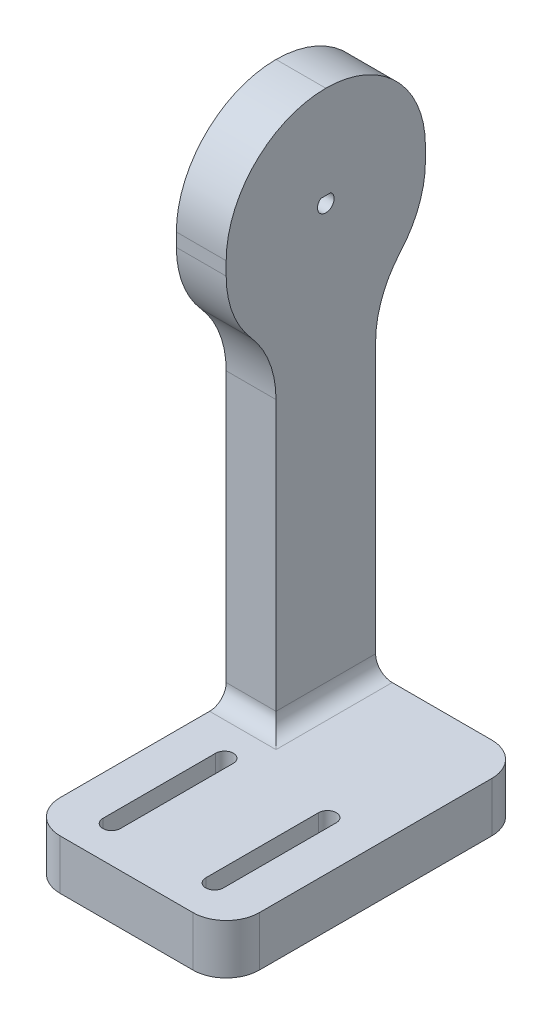
SolidWorks part; units mm, degrees
ref_plane "Front Plane" through (0, 0, 0) normal (0, 0, 1) x (1, 0, 0)
ref_plane "Top Plane" through (0, 0, 0) normal (0, 1, 0) x (1, 0, 0)
ref_plane "Right Plane" through (0, 0, 0) normal (1, 0, 0) x (0, 0, -1)
sketch "Sketch1" plane through (0, 0, 0) normal (1, 0, 0) x (0, 0, -1)
  line L1 (30, -30) -> (-30, -30)
  line L2 (30, -30) -> (30, 30)
  line L3 (30, 30) -> (-30, 30)
  line L4 (-30, -30) -> (-30, 30)
  line L5 (30, -30) -> (-30, 30) construction
  line L6 (30, 30) -> (-30, -30) construction
  point P0 (0, 0)
  dimension "D1" = 60
  dimension "D2" = 60
extrude "Boss-Extrude1" add sketch "Sketch1" along normal blind 15
sketch "Sketch2" plane through (15, 0, 0) normal (1, 0, 0) x (0, 0, -1)
  line L0 (0, 0) -> (0, 30) construction
  line L1 (30, 30) -> (-30, 30) construction
  line L2 (1.5, 2) -> (-1.5, 2)
  circle A0 centre (0, 0) radius 2.5
  dimension "D1" = 5
  dimension "D2" = 3
extrude "Cut-Extrude1" cut sketch "Sketch2" against normal up to surface (15 mm away) contours A0 region at (15, -0.1209, 0) up to face at (0, 0, 0)
sketch "Sketch8" plane through (0, -30, 0) normal (0, -1, 0) x (1, 0, 0)
  line L0 (0, 30) -> (0, 15) construction
  line L1 (0, 30) -> (0, -30) construction
  line L2 (15, 30) -> (15, -30) construction
  line L3 (0, 15) -> (15, 15)
  line L4 (0, 15) -> (0, -15)
  line L5 (0, -15) -> (15, -15)
  line L6 (15, 15) -> (15, -15)
  line L7 (0, -15) -> (0, -30) construction
  dimension "D1" = 30
extrude "Boss-Extrude2" add sketch "Sketch8" along normal blind 100
sketch "Sketch9" plane through (0, -130, 0) normal (0, -1, 0) x (1, 0, 0)
  line L0 (0, 0) -> (0, 75)
  line L1 (0, 15) -> (0, -15) construction
  line L2 (0, 75) -> (60, 75)
  line L3 (60, 75) -> (60, -15)
  line L4 (60, -15) -> (0, -15)
  line L5 (0, -15) -> (0, 0)
  dimension "D1" = 75
  dimension "D2" = 60
  dimension "D3" = 15
extrude "Boss-Extrude3" add sketch "Sketch9" along normal blind 15
sketch "Sketch10" plane through (0, -130, 0) normal (0, 1, 0) x (1, 0, 0)
  line L0 (60, -75) -> (42.85, -75) construction
  line L1 (60, -75) -> (0, -75) construction
  line L2 (42.85, -75) -> (17.15, -75) construction
  line L3 (17.15, -75) -> (0, -75) construction
  line L4 (42.85, -75) -> (42.85, -64) construction
  line L5 (42.85, -64) -> (45.5, -64) construction
  line L6 (48.15, -64) -> (48.15, -30)
  line L7 (42.85, -64) -> (42.85, -30)
  line L8 (42.85, -47) -> (48.15, -47) construction
  line L9 (30, -75) -> (30, -40.6705) construction
  line L10 (17.15, -64) -> (17.15, -30)
  line L11 (11.85, -64) -> (11.85, -30)
  arc A0 (42.85, -64) -> (48.15, -64) centre (45.5, -64) ccw
  arc A1 (42.85, -30) -> (48.15, -30) centre (45.5, -30) cw
  arc A2 (17.15, -30) -> (11.85, -30) centre (14.5, -30) ccw
  arc A3 (17.15, -64) -> (11.85, -64) centre (14.5, -64) cw
  dimension "D1" = 25.7
  dimension "D2" = 11
  dimension "D3" = 2.65
  dimension "D4" = 34
extrude "Cut-Extrude4" cut sketch "Sketch10" against normal up to surface (15 mm away) up to face at (30, -145, 30)
fillet "Fillet1" radius 30 4 edges at (7.5, 30, 30) (7.5, -30, 30) (7.5, -30, -30) (7.5, 30, -30)
fillet "Fillet3" radius 5 2 edges at (7.5, -130, 15) (15, -130, 0)
fillet "Fillet4" radius 10 3 edges at (60, -137.5, 75) (0, -137.5, 75) (60, -137.5, -15)
fillet "Fillet5" radius 30 2 edges at (7.5, -30, 15) (7.5, -30, -15)
